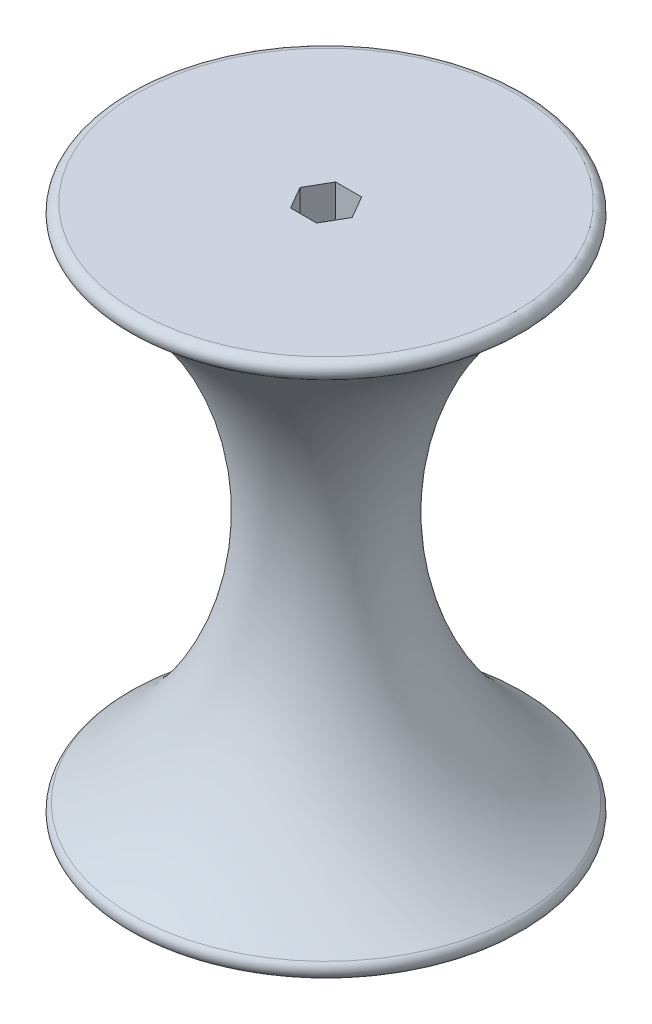
SolidWorks part; units mm, degrees
ref_plane "Front Plane" through (0, 0, 0) normal (0, 0, 1) x (1, 0, 0)
ref_plane "Top Plane" through (0, 0, 0) normal (0, 1, 0) x (1, 0, 0)
ref_plane "Right Plane" through (0, 0, 0) normal (1, 0, 0) x (0, 0, -1)
sketch "Sketch1" plane through (0, 0, 0) normal (0, 0, 1) x (1, 0, 0)
  line L1 (0, -76.2) -> (53.7699, -76.2)
  line L2 (0, -76.2) -> (0, 76.2)
  line L3 (0, 76.2) -> (53.7699, 76.2)
  arc A0 (55.2749, 71.6139) -> (55.2749, -71.6139) centre (107.95, 0) ccw
  arc A1 (55.2749, -71.6139) -> (53.7699, -76.2) centre (53.7699, -73.66) cw
  arc A2 (53.7699, 76.2) -> (55.2749, 71.6139) centre (53.7699, 73.66) cw
  point P10 (19.05, 0)
  point P12 (0, 0)
  dimension "D2" = 88.9
  dimension "D4" = 19.05
  dimension "D3" = 2.54
  dimension "D5" = 152.4
ref_axis "Axis1" through (0, -76.2, 0) along (0, 1, 0)
revolve "Revolve1" add sketch "Sketch1" angle 360 about axis through (0, -76.2, 0) along (0, 1, 0)
sketch "Sketch3" plane through (0, 76.2, 0) normal (0, 1, 0) x (1, 0, 0)
  line L0 (7.4057, 0) -> (3.7028, -6.4135)
  line L1 (3.7028, -6.4135) -> (-3.7028, -6.4135)
  line L2 (-3.7028, -6.4135) -> (-7.4057, 0)
  line L3 (-7.4057, 0) -> (-3.7028, 6.4135)
  line L4 (-3.7028, 6.4135) -> (3.7028, 6.4135)
  line L5 (3.7028, 6.4135) -> (7.4057, 0)
  line L6 (7.4057, 0) -> (-7.4057, 0) construction
  circle A1 centre (0, 0) radius 53.7699
  circle A3 centre (0, 0) radius 53.7699 construction
  point P5 (0, 0)
  dimension "D2" = 12.827
  dimension "D3" = 12.827
  dimension "D1" = 0
extrude "Cut-Extrude1" cut sketch "Sketch3" against normal through all
